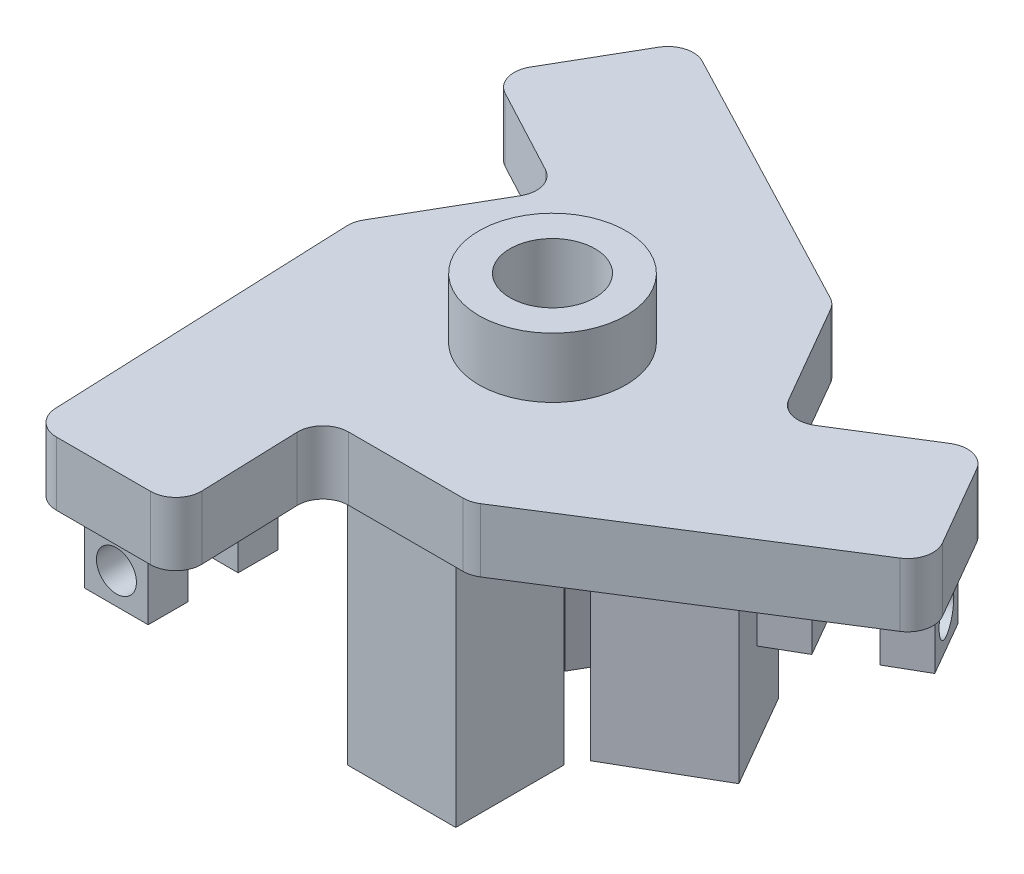
SolidWorks part; units mm, degrees
ref_plane "Front Plane" through (0, 0, 0) normal (0, 0, 1) x (1, 0, 0)
ref_plane "Top Plane" through (0, 0, 0) normal (0, 1, 0) x (1, 0, 0)
ref_plane "Right Plane" through (0, 0, 0) normal (1, 0, 0) x (0, 0, -1)
sketch "Sketch1" plane through (0, 0, 0) normal (0, 1, 0) x (1, 0, 0)
  line L1 (19.05, -32.9956) -> (38.1, 0)
  line L2 (38.1, 0) -> (19.05, 32.9956)
  line L3 (19.05, 32.9956) -> (-19.05, 32.9956)
  line L4 (-19.05, 32.9956) -> (-38.1, 0)
  line L5 (-38.1, 0) -> (-19.05, -32.9956)
  line L6 (-19.05, -32.9956) -> (19.05, -32.9956)
  circle A0 centre (0, 0) radius 32.9956 construction
  dimension "D1" = 38.1
extrude "Boss-Extrude1" add sketch "Sketch1" along normal blind 6.35 contours L4 L5 L6 L1 L2 L3
sketch "Sketch2" plane through (0, 0, 0) normal (0, -1, 0) x (1, 0, 0)
  line L0 (-5.425, 15.1) -> (-5.425, 4.25)
  line L5 (-3.425, 13.1) -> (3.425, 13.1)
  line L6 (-3.425, 13.1) -> (-3.425, 6.25)
  line L7 (-3.425, 6.25) -> (3.425, 6.25)
  line L8 (3.425, 13.1) -> (3.425, 6.25)
  line L9 (-3.425, 13.1) -> (3.425, 6.25) construction
  line L10 (-3.425, 6.25) -> (3.425, 13.1) construction
  line L11 (-5.425, 4.25) -> (-2.067, 4.25)
  line L12 (5.425, 15.1) -> (5.425, 4.25)
  line L13 (-5.425, 15.1) -> (5.425, 15.1)
  line L14 (2.067, 4.25) -> (5.425, 4.25)
  line L15 (-5.425, 4.25) -> (5.425, 4.25) construction
  line L16 (13.0574, -3.5839) -> (7.1252, -0.1589)
  line L17 (13.0574, -3.5839) -> (9.6324, -9.5161)
  line L18 (9.6324, -9.5161) -> (3.7002, -6.0911)
  line L19 (7.1252, -0.1589) -> (3.7002, -6.0911)
  line L20 (2.6471, -3.9151) -> (0.9681, -6.8232)
  line L21 (10.3645, -12.2482) -> (0.9681, -6.8232)
  line L22 (15.7895, -2.8518) -> (10.3645, -12.2482)
  line L23 (15.7895, -2.8518) -> (6.3931, 2.5732)
  line L24 (6.3931, 2.5732) -> (4.7141, -0.3349)
  line L25 (-9.6324, -9.5161) -> (-3.7002, -6.0911)
  line L26 (-9.6324, -9.5161) -> (-13.0574, -3.5839)
  line L27 (-13.0574, -3.5839) -> (-7.1252, -0.1589)
  line L28 (-3.7002, -6.0911) -> (-7.1252, -0.1589)
  line L29 (-4.7141, -0.3349) -> (-6.3931, 2.5732)
  line L30 (-15.7895, -2.8518) -> (-6.3931, 2.5732)
  line L31 (-10.3645, -12.2482) -> (-15.7895, -2.8518)
  line L32 (-10.3645, -12.2482) -> (-0.9681, -6.8232)
  line L33 (-0.9681, -6.8232) -> (-2.6471, -3.9151)
  circle A0 centre (0, 0) radius 4.726 construction
  arc A2 (-2.067, 4.25) -> (2.067, 4.25) centre (0, 0) cw
  arc A3 (4.7141, -0.3349) -> (2.6471, -3.9151) centre (0, 0) cw
  arc A4 (-2.6471, -3.9151) -> (-4.7141, -0.3349) centre (0, 0) cw
  point P3 (0, 9.675)
  point P37 (0, 0)
  dimension "D1" = 9.675
  dimension "D3" = 1.524
  dimension "D4" = 2
  dimension "D2" = 6.85
  dimension "D5" = 3
sketch "Sketch6" plane through (0, 6.35, 0) normal (0, 1, 0) x (1, 0, 0)
  circle A0 centre (0, 0) radius 4.25
  dimension "D1" = 8.5
extrude "Cut-Extrude1" cut sketch "Sketch6" against normal through all
extrude "Boss-Extrude2" add sketch "Sketch2" along normal blind 25.4
sketch "Sketch7" plane through (0, 0, 0) normal (0, -1, 0) x (1, 0, 0)
  line L0 (-14.8153, 22.9723) -> (-8.4653, 22.9723)
  line L1 (-8.4653, 22.9723) -> (-8.4653, 18.9723)
  line L2 (-8.4653, 18.9723) -> (-14.8153, 18.9723)
  line L3 (-14.8153, 18.9723) -> (-14.8153, 22.9723)
  line L4 (-19.05, -32.9956) -> (-38.1, 0) construction
  line L5 (-19.05, 32.9956) -> (19.05, 32.9956) construction
  line L6 (38.1, 0) -> (19.05, -32.9956) construction
  line L7 (-14.8153, 27.9723) -> (-14.8153, 31.9723)
  line L8 (-14.8153, 31.9723) -> (-8.4653, 31.9723)
  line L9 (-8.4653, 31.9723) -> (-8.4653, 27.9723)
  line L10 (-8.4653, 27.9723) -> (-14.8153, 27.9723)
  line L11 (-5.425, 15.1) -> (-5.425, 4.25) construction
  line L12 (27.2966, 1.354) -> (24.1216, -4.1453)
  line L13 (24.1216, -4.1453) -> (20.6575, -2.1453)
  line L14 (20.6575, -2.1453) -> (23.8325, 3.354)
  line L15 (23.8325, 3.354) -> (27.2966, 1.354)
  line L16 (31.6268, -1.146) -> (35.0909, -3.146)
  line L17 (35.0909, -3.146) -> (31.9159, -8.6453)
  line L18 (31.9159, -8.6453) -> (28.4518, -6.6453)
  line L19 (28.4518, -6.6453) -> (31.6268, -1.146)
  line L20 (-12.4813, -24.3068) -> (-15.6563, -18.8076)
  line L21 (-15.6563, -18.8076) -> (-12.1922, -16.8076)
  line L22 (-12.1922, -16.8076) -> (-9.0172, -22.3068)
  line L23 (-9.0172, -22.3068) -> (-12.4813, -24.3068)
  line L24 (-16.8115, -26.8068) -> (-20.2756, -28.8068)
  line L25 (-20.2756, -28.8068) -> (-23.4506, -23.3076)
  line L26 (-23.4506, -23.3076) -> (-19.9865, -21.3076)
  line L27 (-19.9865, -21.3076) -> (-16.8115, -26.8068)
  point P13 (-11.6403, 18.9723)
  dimension "D1" = 22.9723
  dimension "D2" = 4
  dimension "D4" = 5
  dimension "D5" = 6.2153
  dimension "D6" = 6.35
  dimension "D8" = 1.033
  dimension "D9" = 1.033
  dimension "D3" = 2
  dimension "D7" = 3
extrude "Boss-Extrude3" add sketch "Sketch7" along normal blind 6.35
sketch "Sketch9" plane through (0, 0, 31.9723) normal (0, 0, 1) x (1, 0, 0)
  line L0 (-8.4653, -6.35) -> (-14.8153, -6.35) construction
  line L1 (-19.05, 0) -> (19.05, 0) construction
  circle A0 centre (-11.6403, -3.2626) radius 2
  point P4 (-11.6403, -6.35)
  dimension "D1" = 4
  dimension "D2" = 3.2626
extrude "Cut-Extrude2" cut sketch "Sketch9" against normal blind 6.54
pattern_circular "CirPattern1" count 3 over 360 about axis through (0, 0, 0) along (0, 1, 0) of "Cut-Extrude2" reverse direction yes
sketch "Sketch10" plane through (0, 0, 22.9723) normal (0, 0, 1) x (1, 0, 0)
  circle A0 centre (-11.6403, -3.2626) radius 1.7145
  dimension "D1" = 3.429
extrude "Cut-Extrude3" cut sketch "Sketch10" against normal blind 2
pattern_circular "CirPattern2" count 3 over 360 about axis through (0, 0, 0) along (0, 1, 0) of "Cut-Extrude3"
sketch "Sketch11" plane through (0, 0, 0) normal (0, -1, 0) x (1, 0, 0)
  line L0 (-38.1, 0) -> (-19.05, 32.9956)
  line L1 (-19.05, -32.9956) -> (-38.1, 0) construction
  line L2 (-38.1, 0) -> (-19.05, 32.9956) construction
  line L5 (-20.4169, -0.5354) -> (-12.9994, -13.3828)
  line L6 (-12.9994, -13.3828) -> (-26.2859, -20.4626)
  line L7 (-26.2859, -20.4626) -> (-38.1, 0)
  line L21 (-19.05, 32.9956) -> (-20.4169, -0.5354)
  line L22 (19.05, 32.9956) -> (38.1, 0)
  line L23 (9.7447, 17.9492) -> (-5.0901, 17.9492)
  line L24 (-5.0901, 17.9492) -> (-4.5782, 32.9956)
  line L25 (-4.5782, 32.9956) -> (19.05, 32.9956)
  line L26 (38.1, 0) -> (9.7447, 17.9492)
  line L27 (19.05, -32.9956) -> (-19.05, -32.9956)
  line L28 (10.6721, -17.4138) -> (18.0896, -4.5665)
  line L29 (18.0896, -4.5665) -> (30.8641, -12.533)
  line L30 (30.8641, -12.533) -> (19.05, -32.9956)
  line L31 (-19.05, -32.9956) -> (10.6721, -17.4138)
  point P21 (0, 0)
  dimension "D1" = 3
extrude "Cut-Extrude4" cut sketch "Sketch11" against normal up to surface (6.35 mm away) up to face at (0, 6.35, 4.25)
fillet "Fillet1" radius 2.54 12 edges at (18.0896, 3.175, -4.5665) (-12.9994, 3.175, -13.3828) (-5.0901, 3.175, 17.9492) (-19.05, 3.175, 32.9956) (-4.5782, 3.175, 32.9956) (-26.2859, 3.175, -20.4626) (-19.05, 3.175, -32.9956) (30.8641, 3.175, -12.533) (38.1, 3.175, 0) (9.7447, 3.175, 17.9492) (-20.4169, 3.175, -0.5354) (10.6721, 3.175, -17.4138)
sketch "Sketch12" plane through (0, 6.35, 0) normal (0, 1, 0) x (1, 0, 0)
  circle A0 centre (0, 0) radius 7.35
  circle A1 centre (0, 0) radius 4.25
  dimension "D1" = 14.7
  dimension "D2" = 8.5
extrude "Boss-Extrude4" add sketch "Sketch12" along normal blind 6
